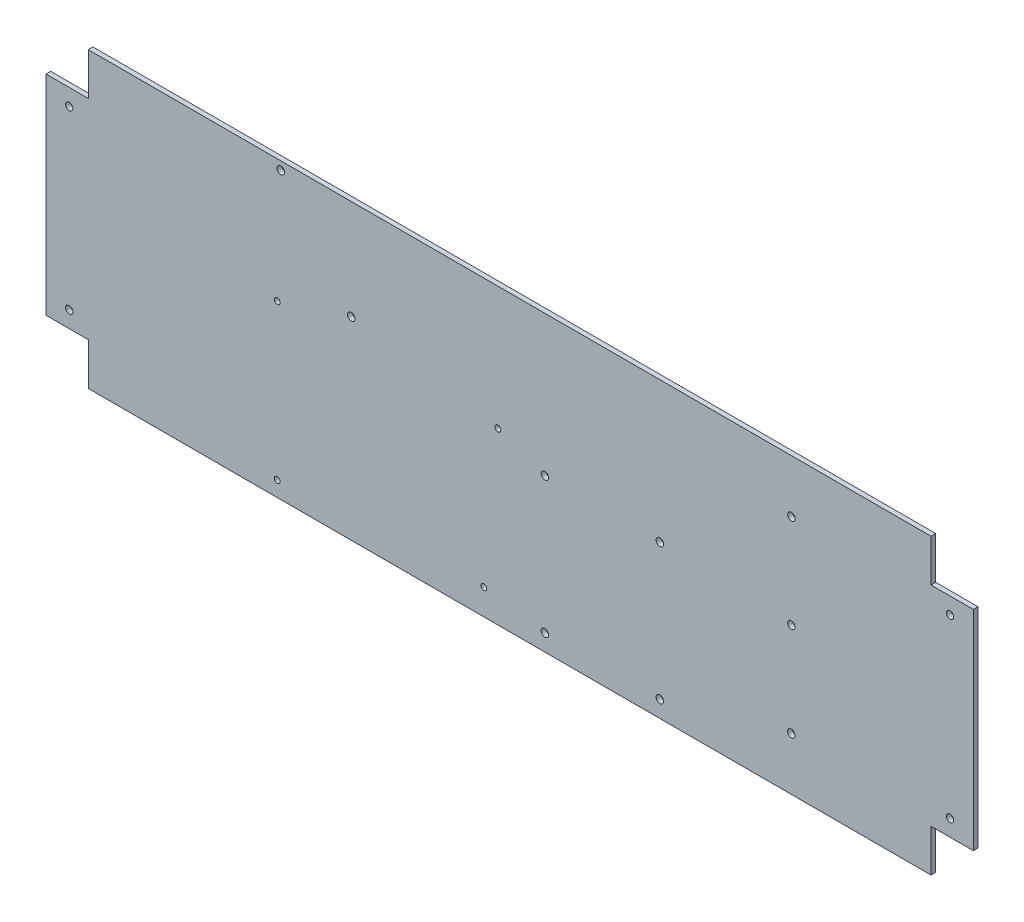
SolidWorks part; units mm, degrees
material "2014 Alloy"
ref_plane "Plan de face" through (0, 0, 0) normal (0, 0, 1) x (1, 0, 0)
ref_plane "Plan de dessus" through (0, 0, 0) normal (0, 1, 0) x (1, 0, 0)
ref_plane "Plan de droite" through (0, 0, 0) normal (1, 0, 0) x (0, 0, -1)
sketch "Sketch1" plane through (0, 0, 0) normal (0, 0, 1) x (1, 0, 0)
  line L1 (-197.5, 62.5) -> (197.5, 62.5)
  line L2 (-197.5, 62.5) -> (-197.5, -62.5)
  line L3 (-197.5, -62.5) -> (197.5, -62.5)
  line L4 (197.5, 62.5) -> (197.5, -62.5)
  line L5 (-197.5, 62.5) -> (197.5, -62.5) construction
  line L6 (-197.5, -62.5) -> (197.5, 62.5) construction
  point P0 (0, 0)
  dimension "D1" = 125
  dimension "D2" = 395
extrude "Boss-Extrude1" add sketch "Sketch1" along normal blind 2
sketch "Sketch2" plane through (0, 0, 2) normal (0, 0, 1) x (1, 0, 0)
  line L1 (-187.6, 37.5) -> (187.6, 37.5) construction
  line L2 (-187.6, 37.5) -> (-187.6, -37.5) construction
  line L3 (-187.6, -37.5) -> (187.6, -37.5) construction
  line L4 (187.6, 37.5) -> (187.6, -37.5) construction
  line L5 (-187.6, 37.5) -> (187.6, -37.5) construction
  line L6 (-187.6, -37.5) -> (187.6, 37.5) construction
  circle A0 centre (-187.6, 37.5) radius 1.55
  circle A1 centre (-187.6, -37.5) radius 1.55
  circle A2 centre (187.6, 37.5) radius 1.55
  circle A3 centre (187.6, -37.5) radius 1.55
  point P0 (0, 0)
  dimension "D1" = 75
  dimension "D2" = 375.2
extrude "Fixing_holes" cut sketch "Sketch2" against normal through all
sketch "Sketch3" plane through (0, 0, 2) normal (0, 0, 1) x (1, 0, 0)
  line L1 (-197.5, 62.5) -> (-179.5, 62.5)
  line L2 (-197.5, 62.5) -> (-197.5, 44.5)
  line L3 (-197.5, 44.5) -> (-179.5, 44.5)
  line L4 (-179.5, 62.5) -> (-179.5, 44.5)
  dimension "D1" = 18
extrude "Cut-Extrude2" cut sketch "Sketch3" against normal through all
mirror "Mirror1" about plane through (0, 0, 0) normal (0, 1, 0) of "Cut-Extrude2"
mirror "Mirror2" about plane through (0, 0, 0) normal (1, 0, 0) of "Mirror1"
sketch "Sketch4" plane through (0, 0, 2) normal (0, 0, 1) x (1, 0, 0)
  line L0 (-99, 10) -> (-5, 10) construction
  line L1 (-99, 10) -> (-99, -56) construction
  circle A0 centre (-99, 10) radius 1.25
  circle A1 centre (-99, -56) radius 1.25
  circle A2 centre (-5, 10) radius 1.25
  circle A3 centre (-11, -51.5) radius 1.25
  dimension "D4" = 66
  dimension "D5" = 94
  dimension "D7" = 61.5
  dimension "D8" = 6
  dimension "D1" = 5
  dimension "D2" = 10
extrude "Cave_board_holes" cut sketch "Sketch4" against normal through all
sketch "Sketch5" plane through (0, 0, 2) normal (0, 0, 1) x (1, 0, 0)
  line L1 (15, 2.6) -> (64, 2.6) construction
  line L2 (15, 2.6) -> (15, -55.4) construction
  line L3 (15, -55.4) -> (64, -55.4) construction
  line L4 (64, 2.6) -> (64, -55.4) construction
  circle A0 centre (15, 2.6) radius 1.6
  circle A1 centre (15, -55.4) radius 1.6
  circle A2 centre (64, 2.6) radius 1.6
  circle A3 centre (64, -55.4) radius 1.6
  dimension "D1" = 58
  dimension "D2" = 49
  dimension "D3" = 15
  dimension "D4" = 2.6
extrude "RPi_holes" cut sketch "Sketch5" against normal through all
sketch "Sketch6" plane through (0, 0, 2) normal (0, 0, 1) x (1, 0, 0)
  line L1 (-97.5, 59) -> (-67.5, 59) construction
  line L2 (-97.5, 59) -> (-97.5, 20) construction
  line L3 (-97.5, 20) -> (-67.5, 20) construction
  line L4 (-67.5, 59) -> (-67.5, 20) construction
  circle A0 centre (-97.5, 59) radius 1.6
  circle A3 centre (-67.5, 20) radius 1.6
  dimension "D1" = 39
  dimension "D2" = 30
  dimension "D3" = 67.5
  dimension "D4" = 20
extrude "buzzer_holes" cut sketch "Sketch6" against normal through all
sketch "Sketch7" plane through (0, 0, 2) normal (0, 0, 1) x (1, 0, 0)
  line L0 (0, 0) -> (178.5314, 0) construction
  circle A0 centre (120, 0) radius 1.6
  circle A1 centre (120, 40) radius 1.6
  circle A2 centre (120, -40) radius 1.6
  dimension "D4" = 120
  dimension "D5" = 40
extrude "relays_holes" cut sketch "Sketch7" against normal through all
